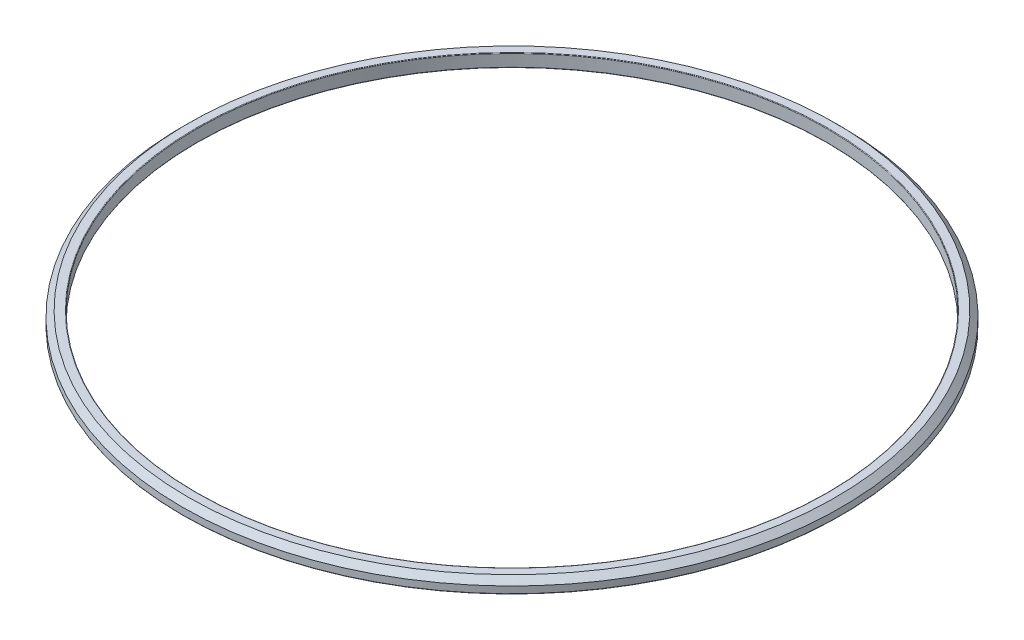
SolidWorks part; units mm, degrees
material "PETG"
ref_plane "Front Plane" through (0, 0, 0) normal (0, 0, 1) x (1, 0, 0)
ref_plane "Top Plane" through (0, 0, 0) normal (0, 1, 0) x (1, 0, 0)
ref_plane "Right Plane" through (0, 0, 0) normal (1, 0, 0) x (0, 0, -1)
sketch "Sketch1" plane through (0, 0, 0) normal (0, 1, 0) x (1, 0, 0)
  circle A0 centre (0, 0) radius 57.235
  circle A1 centre (0, 0) radius 54.765
  dimension "Ring OD" = 114.47
  dimension "Ring ID" = 109.53
extrude "Boss-Extrude1" add sketch "Sketch1" along normal blind 2.25
chamfer "Chamfer1" distance 1 angle 45 1 edges at (0, 2.25, 57.235)
fillet "Fillet1" radius 0.1 3 edges at (0, 2.25, 54.765) (0, 0, 54.765) (0, 0, 57.235)
equation "\"tol_dia_id_intfc\" = 0.0200mm ' For hole diameters - Interference fit"
equation "\"tol_dia_id_slip\"  = 0.0300mm ' For hole diameters - Slip fit"
equation "\"tol_dia_id_clear\" = 0.0500mm ' For hole diameters - Clearance fit"
equation "\"tol_dia_od_intfc\" = 0.0200mm ' For shaft diameters - Interference fit"
equation "\"tol_dia_od_slip\"  = 0.0300mm ' For shaft diameters - Slip fit"
equation "\"tol_dia_od_clear\" = 0.0500mm ' For shaft diameters - Clearance fit"
equation "\"tol_general_intfc\"= 0.0030mm ' For general parts (Horiz) - Interference fit"
equation "\"tol_general_slip\" = 0.0050mm ' For general parts (Horiz) - Slip fit"
equation "\"tol_general_clear\"= 0.0100mm ' For general parts (Horiz) - Clearance fit"
equation "\"tol_layer_intfc\"  = 0.0030mm ' For all parts (Vert) - Interference fit"
equation "\"tol_layer_slip\"   = 0.0050mm ' For all parts (Vert) - Slip fit"
equation "\"tol_layer_clear\"  = 0.0100mm ' For all parts (Vert) - Clearance fit"
equation "\"tol_corner_rad\"   = 0.100mm ' For corners that fit into other parts"
equation "\"Ring OD@Sketch1\"= 114.50mm - \"tol_dia_od_slip\""
equation "\"Ring ID@Sketch1\" = 114.5 - ( 2.5 * 2 ) + \"tol_dia_id_slip\""
equation "\"D1@Fillet1\"=\"tol_corner_rad\""
